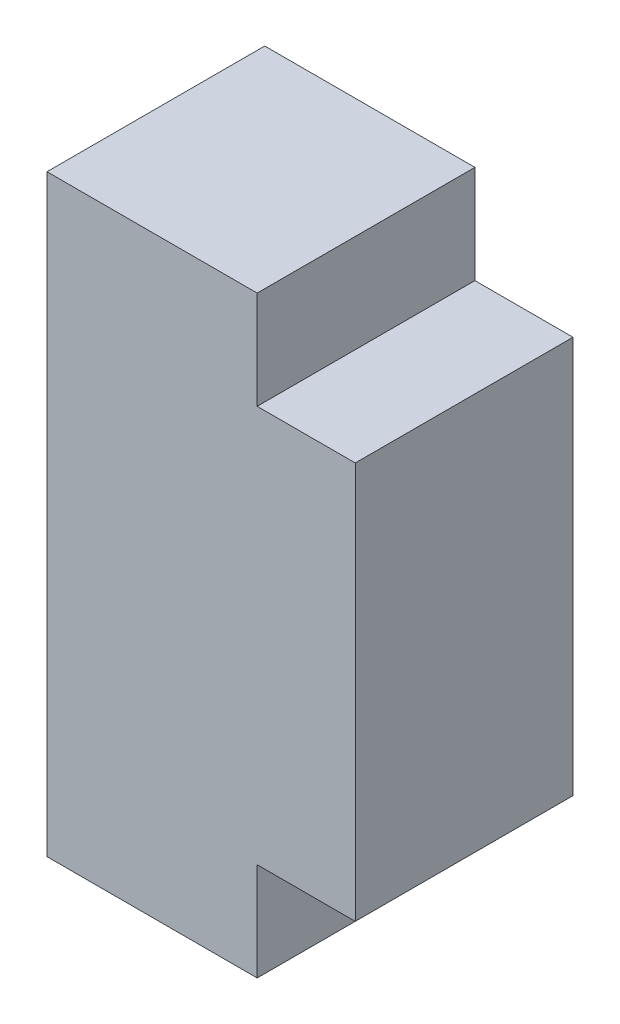
SolidWorks part; units mm, degrees
ref_plane "Front Plane" through (0, 0, 0) normal (0, 0, 1) x (1, 0, 0)
ref_plane "Top Plane" through (0, 0, 0) normal (0, 1, 0) x (1, 0, 0)
ref_plane "Right Plane" through (0, 0, 0) normal (1, 0, 0) x (0, 0, -1)
sketch "Sketch2" plane through (0, 0, 0) normal (0, 0, 1) x (1, 0, 0)
  line L0 (8.25, -152.4) -> (8.25, 152.4) construction
  line L1 (8.25, -39.1052) -> (-8.25, -39.1052)
  line L2 (8.25, -39.1052) -> (8.25, -7.3552)
  line L3 (8.25, -7.3552) -> (-8.25, -7.3552)
  line L4 (-8.25, -39.1052) -> (-8.25, -7.3552)
  line L5 (-8.25, -152.4) -> (-8.25, 152.4) construction
extrude "Boss-Extrude1" add sketch "Sketch2" along normal up to surface (11.655 mm away)
sketch "Sketch3" plane through (0, 0, 11.655) normal (0, 0, 1) x (1, 0, 0)
  line L0 (3.6, -68.5685) -> (3.6, -52.5685) construction
  line L1 (3.6, -72.1685) -> (-3.6, -72.1685)
  line L2 (3.6, -72.1685) -> (3.6, -48.9685)
  line L3 (3.6, -48.9685) -> (-3.6, -48.9685)
  line L4 (-3.6, -72.1685) -> (-3.6, -48.9685)
  line L5 (-4.4, -72.1685) -> (0, -72.1685) construction
  line L6 (0, -48.9685) -> (-4.4, -48.9685) construction
  circle A0 centre (0, -68.5685) radius 2.4 construction
  dimension "D1" = 3.6
extrude "Boss-Extrude2" [suppressed] add sketch "Sketch3" along normal up to surface (6 mm away)
sketch "Sketch4" [suppressed] plane through (0, 0, 11.81) normal (0, 0, 1) x (1, 0, 0)
  circle A4 centre (0, -31.2302) radius 2.8
  circle A5 centre (0, -15.2302) radius 2.8
extrude "Cut-Extrude1" [suppressed] cut sketch "Sketch4" against normal through all
sketch "Sketch5" plane through (0, 0, 11.655) normal (0, 0, 1) x (1, 0, 0)
  line L0 (3, -152.4) -> (3, 152.4) construction
  line L1 (8.25, -39.1052) -> (3, -39.1052)
  line L2 (8.25, -39.1052) -> (8.25, -33.8552)
  line L3 (8.25, -33.8552) -> (3, -33.8552)
  line L4 (3, -39.1052) -> (3, -33.8552)
  line L5 (8.25, -7.3552) -> (3, -7.3552)
  line L6 (8.25, -7.3552) -> (8.25, -12.6052)
  line L7 (8.25, -12.6052) -> (3, -12.6052)
  line L8 (3, -7.3552) -> (3, -12.6052)
extrude "Cut-Extrude2" cut sketch "Sketch5" against normal through all
sketch "Sketch6" plane through (0, 0, 11.655) normal (0, 0, 1) x (1, 0, 0)
  circle A0 centre (0, -52.5685) radius 2.4 construction
  circle A1 centre (0, -68.5685) radius 2.4 construction
  circle A2 centre (0, -52.5685) radius 2.4 construction
  circle A3 centre (0, -68.5685) radius 2.4 construction
  circle A4 centre (0, -68.5685) radius 1.8
  circle A5 centre (0, -52.5685) radius 1.8
  dimension "D1" = 0.6
extrude "Cut-Extrude3" cut sketch "Sketch6" against normal through all rebuild error yes
